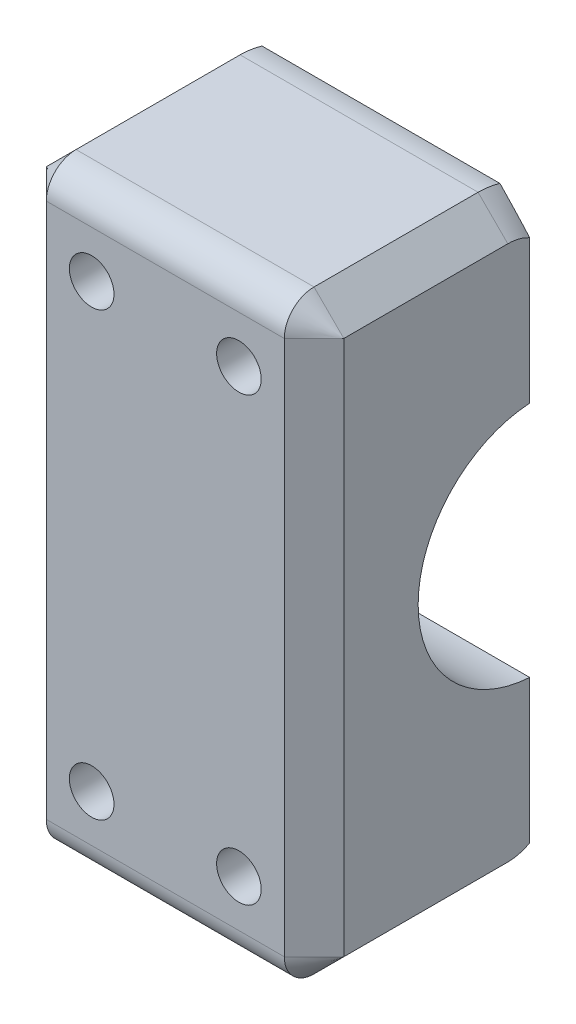
SolidWorks part; units mm, degrees
material "ABS"
ref_plane "Front Plane" through (0, 0, 0) normal (0, 0, 1) x (1, 0, 0)
ref_plane "Top Plane" through (0, 0, 0) normal (0, 1, 0) x (1, 0, 0)
ref_plane "Right Plane" through (0, 0, 0) normal (1, 0, 0) x (0, 0, -1)
sketch "Sketch1" plane through (0, 0, 0) normal (0, 0, 1) x (1, 0, 0)
  line L8 (10.6892, 89.7411) -> (30.6892, 89.7411)
  line L9 (30.6892, 89.7411) -> (30.6892, 139.3411)
  line L10 (30.6892, 139.3411) -> (10.6892, 139.3411)
  line L11 (10.6892, 139.3411) -> (10.6892, 89.7411)
  circle A4 centre (15.7395, 99.6914) radius 1.5
  circle A5 centre (25.639, 99.6914) radius 1.5
  circle A6 centre (25.639, 129.3909) radius 1.5
  circle A7 centre (15.7395, 129.3909) radius 1.5
sketch "Sketch2" plane through (0, 0, 0) normal (0, 0, 1) x (1, 0, 0)
  line L0 (10.6892, 89.7411) -> (30.6892, 89.7411) construction
  line L1 (30.6892, 89.7411) -> (30.6892, 139.3411) construction
  line L2 (10.6892, 139.3411) -> (10.6892, 89.7411) construction
  line L3 (30.6892, 139.3411) -> (10.6892, 139.3411) construction
  line L4 (10.6892, 89.7411) -> (30.6892, 89.7411)
  line L5 (30.6892, 89.7411) -> (30.6892, 139.3411)
  line L6 (10.6892, 139.3411) -> (10.6892, 89.7411)
  line L7 (30.6892, 139.3411) -> (10.6892, 139.3411)
  circle A0 centre (15.7395, 99.6914) radius 1.5 construction
  circle A1 centre (25.639, 99.6914) radius 1.5 construction
  circle A2 centre (25.639, 129.3909) radius 1.5 construction
  circle A3 centre (15.7395, 129.3909) radius 1.5 construction
  circle A4 centre (15.7395, 99.6914) radius 1.5
  circle A5 centre (25.639, 99.6914) radius 1.5
  circle A6 centre (25.639, 129.3909) radius 1.5
  circle A7 centre (15.7395, 129.3909) radius 1.5
extrude "Boss-Extrude1" add sketch "Sketch2" along normal blind 30
sketch "Sketch3" plane through (30.6892, 0, 0) normal (1, 0, 0) x (0, 0, -1)
  line L0 (-30, 139.3411) -> (0, 89.7411)
  line L2 (-20, 109.5411) -> (-10, 109.5411)
  line L3 (-20, 109.5411) -> (-20, 119.5411)
  line L4 (0, 89.7411) -> (0, 139.3411)
  line L5 (0, 139.3411) -> (-30, 139.3411)
  line L6 (-30, 139.3411) -> (-30, 89.7411)
  line L7 (-30, 89.7411) -> (0, 89.7411)
  line L8 (0, 89.7411) -> (0, 139.3411)
  line L9 (0, 139.3411) -> (-30, 139.3411)
  line L10 (-30, 139.3411) -> (-30, 89.7411)
  line L11 (-30, 89.7411) -> (0, 89.7411)
  line L12 (-20, 119.5411) -> (-10, 119.5411)
  line L13 (-10, 109.5411) -> (-10, 119.5411)
  line L14 (-20, 109.5411) -> (-10, 119.5411) construction
  line L15 (-20, 119.5411) -> (-10, 109.5411) construction
  point P2 (-15, 114.5411)
  dimension "D2" = 10
  dimension "D1" = 0
extrude "Cut-Extrude1" cut sketch "Sketch3" against normal blind 30 contours L2 L13 L12 L0 | L12 L3 L2 L0 region at (30.6892, 115.5492, 12.8049) region at (30.6892, 113.533, 17.1951)
sketch "Sketch4" plane through (30.6892, 0, 0) normal (1, 0, 0) x (0, 0, -1)
  line L0 (0, 89.7411) -> (-30, 139.3411)
  line L1 (0, 120.5411) -> (0, 108.5411)
  line L2 (-30, 134.5411) -> (0, 134.5411)
  line L3 (-30, 134.5411) -> (-30, 94.5411)
  line L4 (0, 89.7411) -> (0, 139.3411)
  line L5 (0, 139.3411) -> (-30, 139.3411)
  line L6 (-30, 139.3411) -> (-30, 89.7411)
  line L7 (-30, 89.7411) -> (0, 89.7411)
  line L8 (0, 89.7411) -> (0, 139.3411)
  line L9 (0, 139.3411) -> (-30, 139.3411)
  line L10 (-30, 139.3411) -> (-30, 89.7411)
  line L11 (-30, 89.7411) -> (0, 89.7411)
  line L12 (-30, 94.5411) -> (0, 94.5411)
  line L13 (0, 134.5411) -> (0, 94.5411)
  line L14 (-30, 134.5411) -> (0, 94.5411) construction
  line L15 (-30, 94.5411) -> (0, 134.5411) construction
  line L16 (-15, 134.5411) -> (0, 120.5411)
  line L17 (-30, 114.5411) -> (0, 114.5411)
  line L18 (-15, 94.5411) -> (0, 108.5411)
  point P2 (-15, 114.5411)
  point P13 (0, 114.5411)
  line M16 (0, 89.7411) -> (0, 139.3411)
  line M17 (0, 139.3411) -> (-30, 139.3411)
  line M18 (-30, 139.3411) -> (-30, 89.7411)
  line M19 (-30, 89.7411) -> (0, 89.7411)
  dimension "D2" = 40
  dimension "D3" = 12
  dimension "D1" = 0
extrude "Cut-Extrude2" cut sketch "Sketch4" against normal blind 22 contours L0 L2 M16 M17 | L2 L0 M18 | L2 L16 M16 | L18 L0 L12 L8 | L18 L12 L0 | L12 L0 M18 M19 | L12 L0 M16 region at (30.6892, 92.1004, 15.7135) region at (30.6892, 92.9411, 0.9677) region at (30.6892, 96.9466, 8.3904) region at (30.6892, 100.8165, 2.5879) region at (30.6892, 136.1411, 29.0323) region at (30.6892, 136.9818, 14.2865) region at (30.6892, 129.8744, 5)
fillet "Fillet1" radius 5 4 edges at (20.6892, 134.5411, 15) (20.6892, 94.5411, 15) (20.6892, 120.5411, 0) (20.6892, 108.5411, 0)
fillet "Fillet2" radius 2 2 edges at (20.6892, 94.5411, 30) (20.6892, 134.5411, 30)
chamfer "Chamfer1" distance 2 angle 45 24 edges at (30.6892, 134.5411, 22.4854) (30.6892, 133.9553, 29.4142) (30.6892, 134.1928, 15.1373) (30.6892, 114.5411, 30) (30.6892, 127.61, 7.5738) (30.6892, 95.1269, 29.4142) (30.6892, 120.3611, 0.4143) (30.6892, 94.5411, 22.4854) (30.6892, 114.5411, 0) (30.6892, 94.8894, 15.1373) (30.6892, 108.7211, 0.4143) (30.6892, 101.4722, 7.5738) (10.6892, 134.5411, 22.4854) (10.6892, 133.9553, 29.4142) (10.6892, 134.1928, 15.1373) (10.6892, 114.5411, 30) (10.6892, 127.61, 7.5738) (10.6892, 95.1269, 29.4142) (10.6892, 120.3611, 0.4143) (10.6892, 94.5411, 22.4854) (10.6892, 114.5411, 0) (10.6892, 94.8894, 15.1373) (10.6892, 108.7211, 0.4143) (10.6892, 101.4722, 7.5738)
sketch "Sketch5" plane through (0, 0, 0) normal (0, 0, -1) x (-1, 0, 0)
  circle A0 centre (-15.7395, 129.3909) radius 1.5 construction
  circle A1 centre (-25.639, 129.3909) radius 1.5 construction
  circle A2 centre (-25.639, 99.6914) radius 1.5 construction
  circle A3 centre (-15.7395, 99.6914) radius 1.5 construction
  circle A4 centre (-15.7395, 129.3909) radius 1.5
  circle A5 centre (-25.639, 129.3909) radius 1.5
  circle A6 centre (-25.639, 99.6914) radius 1.5
  circle A7 centre (-15.7395, 99.6914) radius 1.5
  circle A8 centre (-15.7395, 99.6914) radius 3
  circle A9 centre (-25.639, 99.6914) radius 3
  circle A10 centre (-15.7395, 129.3909) radius 3
  circle A11 centre (-25.639, 129.3909) radius 3
  dimension "D1" = 1.5
extrude "Cut-Extrude3" cut sketch "Sketch5" against normal blind 12
sketch "Sketch6" plane through (10.6892, 0, 0) normal (-1, 0, 0) x (0, 0, 1)
  line L0 (10, 109.5411) -> (20, 119.5411)
  line L1 (15, 137.8794) -> (15, 91.2028)
  line L2 (15.5, 137.8794) -> (15.5, 91.2028)
  line L3 (15.5, 137.8794) -> (15.5, 91.2028)
  line L4 (15.5, 137.8794) -> (-6.9537, 137.8794)
  line L5 (15.5, 91.2028) -> (-6.9537, 91.2028)
  line L6 (-6.9537, 137.8794) -> (-6.9537, 91.2028)
  circle A0 centre (15, 114.5411) radius 8
  point P9 (15, 114.5411)
  arc M4 (16.9708, 132.5411) -> (14.9239, 131.7343) centre (16.9708, 129.5411) ccw
  line M5 (14.9239, 131.7343) -> (2.953, 120.5615)
  arc M6 (2.953, 120.5615) -> (2, 118.3683) centre (5, 118.3683) ccw
  line M7 (2, 118.3683) -> (2, 110.7139)
  arc M8 (2, 110.7139) -> (2.953, 108.5207) centre (5, 110.7139) ccw
  line M9 (2.953, 108.5207) -> (14.9239, 97.3479)
  arc M10 (14.9239, 97.3479) -> (16.9708, 96.5411) centre (16.9708, 99.5411) ccw
  line M12 (20, 119.5411) -> (20, 109.5411)
  line M13 (20, 109.5411) -> (10, 109.5411)
  line M14 (10, 109.5411) -> (10, 119.5411)
  line M15 (10, 119.5411) -> (20, 119.5411)
  dimension "D1" = 16
  dimension "D2" = 0.5
extrude "Cut-Extrude4" cut sketch "Sketch6" against normal blind 23 contours L4 L6 L5 L1 M10 M9 M8 M7 M6 M5 M4 | L3 A0 L1 M15 | L2 A0 L3 M15 M12 M13 | L1 A0 M13 M14 M15 | L1 L0 M15 M14 | L2 L1 L0 M15 | L2 L0 M15 | L0 L2 M13 M12 | L2 L0 L1 M13 | L1 L0 M13 | L1 A0 L2 M13 | A0 L2 L1 M4 | L5 L2 L1 M10 | A0 L1 L3 M10 | A0 L1 M4 M5 M6 M7 M8 M9 M10 | L2 L4 L1 M4 region at (10.6892, 115.6522, 12.2222) region at (10.6892, 111.2078, 13.3333) region at (10.6892, 109.3622, 12.5) region at (10.6892, 117.1639, 15.2456) region at (10.6892, 112.1681, 15.254) region at (10.6892, 108.0437, 15.2498) region at (10.6892, 118.0411, 17) region at (10.6892, 113.525, 17.9677) region at (10.6892, 121.0385, 15.2498) region at (10.6892, 101.8176, 15.2516) region at (10.6892, 101.9102, 14.6311) region at (10.6892, 109.3647, 17.75) region at (10.6892, 127.2646, 15.2516) region at (10.6892, 94.1473, 15.2475) region at (10.6892, 114.5411, 1.7808) region at (10.6892, 134.9349, 15.2475)
